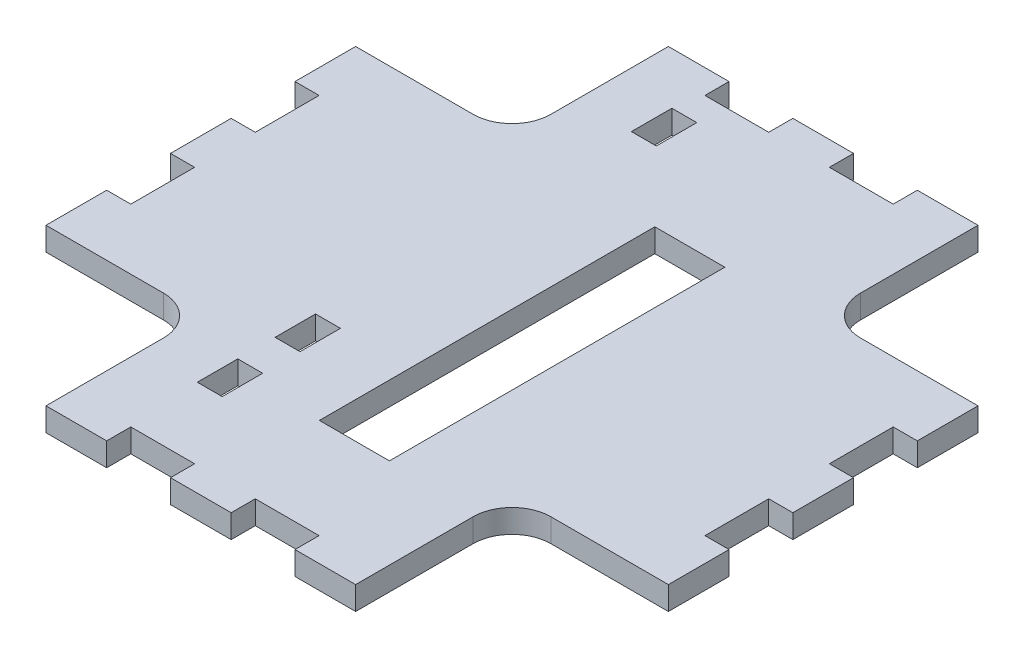
SolidWorks part; units mm, degrees
ref_plane "Front Plane" through (0, 0, 0) normal (0, 0, 1) x (1, 0, 0)
ref_plane "Top Plane" through (0, 0, 0) normal (0, 1, 0) x (1, 0, 0)
ref_plane "Right Plane" through (0, 0, 0) normal (1, 0, 0) x (0, 0, -1)
sketch "Sketch1" plane through (0, 0, 0) normal (0, 1, 0) x (1, 0, 0)
  line L0 (80, 0) -> (80, 80) construction
  line L1 (0, 0) -> (80, 0)
  line L2 (0, 0) -> (0, 80)
  line L3 (0, 80) -> (80, 80)
  line L4 (80, 0) -> (80, 80)
  line L5 (80, 80) -> (0, 80) construction
  line L7 (39.3, 15.9432) -> (48.3, 15.9432)
  line L8 (39.3, 15.9432) -> (39.3, 59.0568)
  line L9 (39.3, 59.0568) -> (48.3, 59.0568)
  line L10 (48.3, 15.9432) -> (48.3, 59.0568)
  line L12 (45.3, 15.9432) -> (45.3, 59.0568) construction
  line L13 (42.3, 59.0568) -> (42.3, 15.9432) construction
  line L14 (45.3, 16.5) -> (45.3, 58.5) construction
  line L15 (42.3, 16.5) -> (42.3, 58.5) construction
  line L17 (45.3, 37.5) -> (48.3, 37.5) construction
  line L18 (42.3, 40) -> (39.3, 40) construction
  line L20 (42.3, 37.5) -> (39.3, 37.5) construction
sketch "Sketch2" plane through (0, 0, 0) normal (0, 0, 1) x (1, 0, 0)
  line L1 (0, 0) -> (80, 0)
  line L2 (0, 0) -> (0, -3)
  line L3 (0, -3) -> (80, -3)
  line L4 (80, 0) -> (80, -3)
extrude "Boss-Extrude1" add sketch "Sketch1" against normal up to vertex (3 mm away) up to point (0, -3, 0)
sketch "Sketch3" plane through (0, 0, 0) normal (0, 1, 0) x (1, 0, 0)
  line L8 (36, 3) -> (28, 3)
  line L9 (28, 3) -> (28, 0)
  line L10 (28, 0) -> (36, 0)
  line L11 (36, 0) -> (36, 3)
  line L12 (36, 3) -> (28, 3) construction
  line L13 (28, 3) -> (28, 0) construction
  line L14 (28, 0) -> (36, 0) construction
  line L15 (36, 0) -> (36, 3) construction
  line L16 (77, 28) -> (80, 28)
  line L17 (77, 36) -> (77, 28)
  line L18 (80, 36) -> (77, 36)
  line L19 (80, 28) -> (80, 36)
  line L20 (77, 28) -> (80, 28) construction
  line L21 (77, 36) -> (77, 28) construction
  line L22 (80, 36) -> (77, 36) construction
  line L23 (80, 28) -> (80, 36) construction
  line L24 (44, 3) -> (44, 0)
  line L25 (52, 3) -> (44, 3)
  line L26 (52, 0) -> (52, 3)
  line L27 (44, 0) -> (52, 0)
  line L28 (44, 3) -> (44, 0) construction
  line L29 (52, 3) -> (44, 3) construction
  line L30 (52, 0) -> (52, 3) construction
  line L31 (44, 0) -> (52, 0) construction
  line L32 (0, 28) -> (3, 28)
  line L33 (0, 36) -> (0, 28)
  line L34 (3, 36) -> (0, 36)
  line L35 (3, 28) -> (3, 36)
  line L36 (0, 28) -> (3, 28) construction
  line L37 (0, 36) -> (0, 28) construction
  line L38 (3, 36) -> (0, 36) construction
  line L39 (3, 28) -> (3, 36) construction
  line L40 (20, 20) -> (0, 20)
  line L41 (0, 20) -> (0, 0)
  line L42 (0, 0) -> (20, 0)
  line L43 (20, 0) -> (20, 20)
  line L44 (20, 20) -> (0, 20) construction
  line L45 (0, 20) -> (0, 0) construction
  line L46 (0, 0) -> (20, 0) construction
  line L47 (20, 0) -> (20, 20) construction
  line L48 (60, 20) -> (60, 0)
  line L49 (80, 20) -> (60, 20)
  line L50 (80, 0) -> (80, 20)
  line L51 (60, 0) -> (80, 0)
  line L52 (60, 20) -> (60, 0) construction
  line L53 (80, 20) -> (60, 20) construction
  line L54 (80, 0) -> (80, 20) construction
  line L55 (60, 0) -> (80, 0) construction
  line L56 (36, 77) -> (36, 80)
  line L57 (28, 77) -> (36, 77)
  line L58 (28, 80) -> (28, 77)
  line L59 (36, 80) -> (28, 80)
  line L60 (36, 77) -> (36, 80) construction
  line L61 (28, 77) -> (36, 77) construction
  line L62 (28, 80) -> (28, 77) construction
  line L63 (36, 80) -> (28, 80) construction
  line L64 (0, 52) -> (0, 44)
  line L65 (0, 44) -> (3, 44)
  line L66 (3, 44) -> (3, 52)
  line L67 (3, 52) -> (0, 52)
  line L68 (0, 52) -> (0, 44) construction
  line L69 (0, 44) -> (3, 44) construction
  line L70 (3, 44) -> (3, 52) construction
  line L71 (3, 52) -> (0, 52) construction
  line L72 (20, 60) -> (20, 80)
  line L73 (0, 60) -> (20, 60)
  line L74 (0, 80) -> (0, 60)
  line L75 (20, 80) -> (0, 80)
  line L76 (20, 60) -> (20, 80) construction
  line L77 (0, 60) -> (20, 60) construction
  line L78 (0, 80) -> (0, 60) construction
  line L79 (20, 80) -> (0, 80) construction
  line L80 (80, 52) -> (77, 52)
  line L81 (80, 44) -> (80, 52)
  line L82 (77, 44) -> (80, 44)
  line L83 (77, 52) -> (77, 44)
  line L84 (80, 52) -> (77, 52) construction
  line L85 (80, 44) -> (80, 52) construction
  line L86 (77, 44) -> (80, 44) construction
  line L87 (77, 52) -> (77, 44) construction
  line L88 (80, 80) -> (60, 80)
  line L89 (80, 60) -> (80, 80)
  line L90 (60, 60) -> (80, 60)
  line L91 (60, 80) -> (60, 60)
  line L92 (80, 80) -> (60, 80) construction
  line L93 (80, 60) -> (80, 80) construction
  line L94 (60, 60) -> (80, 60) construction
  line L95 (60, 80) -> (60, 60) construction
  line L96 (52, 77) -> (52, 80)
  line L97 (44, 77) -> (52, 77)
  line L98 (44, 80) -> (44, 77)
  line L99 (52, 80) -> (44, 80)
  line L144 (52, 77) -> (52, 80) construction
  line L145 (44, 77) -> (52, 77) construction
  line L146 (44, 80) -> (44, 77) construction
  line L147 (52, 80) -> (44, 80) construction
  line L148 (30.3, 17.45) -> (27.3, 17.45)
  line L149 (27.3, 17.45) -> (27.3, 12.45)
  line L150 (27.3, 12.45) -> (30.3, 12.45)
  line L151 (30.3, 12.45) -> (30.3, 17.45)
  line L152 (30.3, 17.45) -> (27.3, 17.45) construction
  line L153 (27.3, 17.45) -> (27.3, 12.45) construction
  line L154 (27.3, 12.45) -> (30.3, 12.45) construction
  line L155 (30.3, 12.45) -> (30.3, 17.45) construction
  line L156 (30.3, 22.45) -> (30.3, 27.45)
  line L157 (30.3, 27.45) -> (27.3, 27.45)
  line L158 (27.3, 27.45) -> (27.3, 22.45)
  line L159 (27.3, 22.45) -> (30.3, 22.45)
  line L160 (30.3, 22.45) -> (30.3, 27.45) construction
  line L161 (30.3, 27.45) -> (27.3, 27.45) construction
  line L162 (27.3, 27.45) -> (27.3, 22.45) construction
  line L163 (27.3, 22.45) -> (30.3, 22.45) construction
  line L164 (27.3, 68.25) -> (30.3, 68.25)
  line L165 (30.3, 68.25) -> (30.3, 73.25)
  line L166 (30.3, 73.25) -> (27.3, 73.25)
  line L167 (27.3, 73.25) -> (27.3, 68.25)
  line L168 (27.3, 68.25) -> (30.3, 68.25) construction
  line L169 (30.3, 68.25) -> (30.3, 73.25) construction
  line L170 (30.3, 73.25) -> (27.3, 73.25) construction
  line L171 (27.3, 73.25) -> (27.3, 68.25) construction
  line L564 (36.1, 3.1) -> (27.9, 3.1)
  line L565 (27.9, 3.1) -> (27.9, -0.1)
  line L566 (27.9, -0.1) -> (36.1, -0.1)
  line L567 (36.1, -0.1) -> (36.1, 3.1)
  line L568 (76.9, 27.9) -> (80.1, 27.9)
  line L569 (80.1, 27.9) -> (80.1, 36.1)
  line L570 (80.1, 36.1) -> (76.9, 36.1)
  line L571 (76.9, 36.1) -> (76.9, 27.9)
  line L572 (43.9, 3.1) -> (43.9, -0.1)
  line L573 (43.9, -0.1) -> (52.1, -0.1)
  line L574 (52.1, -0.1) -> (52.1, 3.1)
  line L575 (52.1, 3.1) -> (43.9, 3.1)
  line L576 (-0.1, 27.9) -> (3.1, 27.9)
  line L577 (3.1, 27.9) -> (3.1, 36.1)
  line L578 (3.1, 36.1) -> (-0.1, 36.1)
  line L579 (-0.1, 36.1) -> (-0.1, 27.9)
  line L580 (20.1, 20.1) -> (-0.1, 20.1)
  line L581 (-0.1, 20.1) -> (-0.1, -0.1)
  line L582 (-0.1, -0.1) -> (20.1, -0.1)
  line L583 (20.1, -0.1) -> (20.1, 20.1)
  line L584 (59.9, 20.1) -> (59.9, -0.1)
  line L585 (59.9, -0.1) -> (80.1, -0.1)
  line L586 (80.1, -0.1) -> (80.1, 20.1)
  line L587 (80.1, 20.1) -> (59.9, 20.1)
  line L588 (36.1, 76.9) -> (36.1, 80.1)
  line L589 (36.1, 80.1) -> (27.9, 80.1)
  line L590 (27.9, 80.1) -> (27.9, 76.9)
  line L591 (27.9, 76.9) -> (36.1, 76.9)
  line L592 (-0.1, 52.1) -> (-0.1, 43.9)
  line L593 (-0.1, 43.9) -> (3.1, 43.9)
  line L594 (3.1, 43.9) -> (3.1, 52.1)
  line L595 (3.1, 52.1) -> (-0.1, 52.1)
  line L596 (20.1, 59.9) -> (20.1, 80.1)
  line L597 (20.1, 80.1) -> (-0.1, 80.1)
  line L598 (-0.1, 80.1) -> (-0.1, 59.9)
  line L599 (-0.1, 59.9) -> (20.1, 59.9)
  line L600 (80.1, 52.1) -> (76.9, 52.1)
  line L601 (76.9, 52.1) -> (76.9, 43.9)
  line L602 (76.9, 43.9) -> (80.1, 43.9)
  line L603 (80.1, 43.9) -> (80.1, 52.1)
  line L604 (80.1, 80.1) -> (59.9, 80.1)
  line L605 (59.9, 80.1) -> (59.9, 59.9)
  line L606 (59.9, 59.9) -> (80.1, 59.9)
  line L607 (80.1, 59.9) -> (80.1, 80.1)
  line L608 (52.1, 76.9) -> (52.1, 80.1)
  line L609 (52.1, 80.1) -> (43.9, 80.1)
  line L610 (43.9, 80.1) -> (43.9, 76.9)
  line L611 (43.9, 76.9) -> (52.1, 76.9)
  line L612 (30.4, 17.55) -> (27.2, 17.55)
  line L613 (27.2, 17.55) -> (27.2, 12.35)
  line L614 (27.2, 12.35) -> (30.4, 12.35)
  line L615 (30.4, 12.35) -> (30.4, 17.55)
  line L616 (30.4, 22.35) -> (30.4, 27.55)
  line L617 (30.4, 27.55) -> (27.2, 27.55)
  line L618 (27.2, 27.55) -> (27.2, 22.35)
  line L619 (27.2, 22.35) -> (30.4, 22.35)
  line L620 (27.2, 68.15) -> (30.4, 68.15)
  line L621 (30.4, 68.15) -> (30.4, 73.35)
  line L622 (30.4, 73.35) -> (27.2, 73.35)
  line L623 (27.2, 73.35) -> (27.2, 68.15)
  dimension "D1" = 0
  dimension "D2" = 0
  dimension "D3" = 0
  dimension "D4" = 0
  dimension "D5" = 0
  dimension "D6" = 0
  dimension "D7" = 0
  dimension "D8" = 0
  dimension "D9" = 0
  dimension "D10" = 0
  dimension "D11" = 0
  dimension "D12" = 0
  dimension "D13" = 0
  dimension "D14" = 0
  dimension "D15" = 0
  dimension "D16" = 0.1
extrude "Cut-Extrude1" cut sketch "Sketch3" against normal through all
fillet "Fillet1" radius 5 4 edges at (20.1, -1.5, -20.1) (20.1, -1.5, -59.9) (59.9, -1.5, -59.9) (59.9, -1.5, -20.1)
